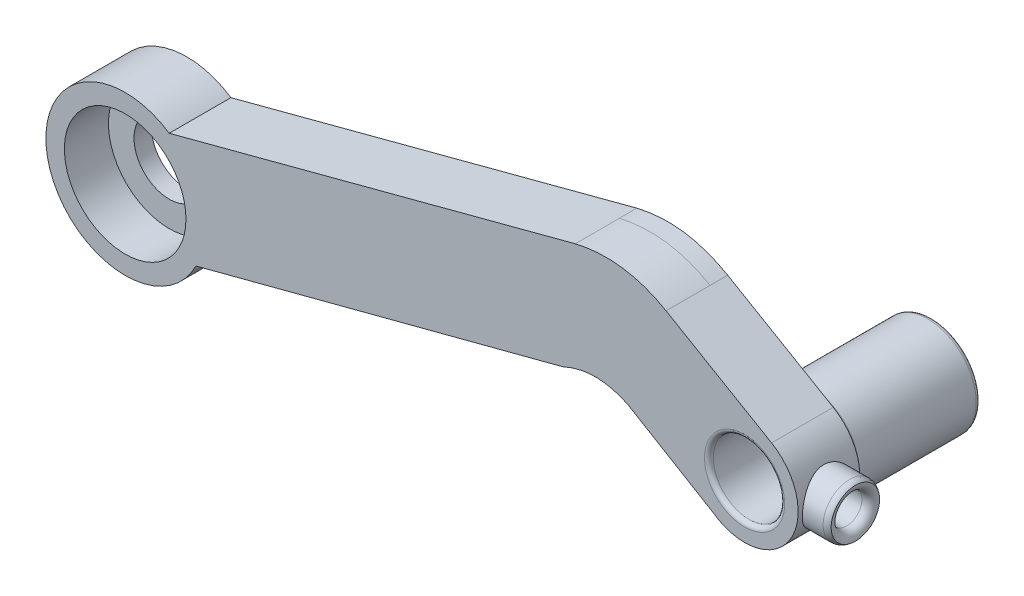
SolidWorks part; units mm, degrees
ref_plane "Front Plane" through (0, 0, 0) normal (0, 0, 1) x (1, 0, 0)
ref_plane "Top Plane" through (0, 0, 0) normal (0, 1, 0) x (1, 0, 0)
ref_plane "Right Plane" through (0, 0, 0) normal (1, 0, 0) x (0, 0, -1)
sketch "Sketch2" plane through (0, 0, 102.4316) normal (0, 0, 1) x (1, 0, 0)
  line L8 (-120.223, 48.1324) -> (-110.6681, 42.4279)
  line L9 (-169.3666, 37.3143) -> (-127.7161, 48.234)
  line L10 (-126.3187, 61.0272) -> (-172.4039, 48.8476)
  line L11 (-104.0278, 52.5928) -> (-116.0098, 59.5925)
  circle A2 centre (-107.0939, 47.3443) radius 4.05
  circle A3 centre (-177.4038, 41.3642) radius 6.9
  arc A5 (-110.6681, 42.4279) -> (-104.0278, 52.5928) centre (-107.0939, 47.3443) ccw
  arc A6 (-172.4039, 48.8476) -> (-169.3666, 37.3143) centre (-177.4038, 41.3642) ccw
  parabola Q4 (-127.7161, 48.234) -> (-120.223, 48.1324) focus (-123.8474, 45.2368) apex (-123.6641, 49.0843)
  parabola Q5 (-116.0098, 59.5925) -> (-126.3187, 61.0272) focus (-121.5094, 54.8565) apex (-120.2687, 61.2162)
extrude "Boss-Extrude1" add sketch "Sketch2" along normal blind 5
sketch "Sketch3" plane through (0, 0, 102.4316) normal (0, 0, -1) x (-1, 0, 0)
  line L4 (110.6681, 42.4279) -> (120.223, 48.1324)
  line L5 (127.7161, 48.234) -> (169.3666, 37.3143)
  line L6 (172.4039, 48.8476) -> (126.3187, 61.0272)
  line L7 (116.0098, 59.5925) -> (104.0278, 52.5928)
  line L8 (110.6681, 42.4279) -> (120.223, 48.1324)
  line L9 (127.7161, 48.234) -> (169.3666, 37.3143)
  line L10 (172.4039, 48.8476) -> (126.3187, 61.0272)
  line L11 (116.0098, 59.5925) -> (104.0278, 52.5928)
  circle A0 centre (107.0939, 47.3443) radius 4.05
  circle A1 centre (177.4038, 41.3642) radius 4
  arc A2 (104.0278, 52.5928) -> (110.6681, 42.4279) centre (107.0939, 47.3443) ccw
  arc A3 (169.3666, 37.3143) -> (172.4039, 48.8476) centre (177.4038, 41.3642) ccw
  arc A4 (104.0278, 52.5928) -> (110.6681, 42.4279) centre (107.0939, 47.3443) ccw
  arc A5 (169.3666, 37.3143) -> (172.4039, 48.8476) centre (177.4038, 41.3642) ccw
  parabola Q2 (120.223, 48.1324) -> (127.7161, 48.234) focus (123.8474, 45.2368) apex (123.6641, 49.0843)
  parabola Q3 (126.3187, 61.0272) -> (116.0098, 59.5925) focus (121.5094, 54.8565) apex (120.2687, 61.2162)
  parabola Q4 (120.223, 48.1324) -> (127.7161, 48.234) focus (123.8474, 45.2368) apex (123.6641, 49.0843)
  parabola Q5 (126.3187, 61.0272) -> (116.0098, 59.5925) focus (121.5094, 54.8565) apex (120.2687, 61.2162)
  dimension "D2" = 8.1
  dimension "D3" = 8
  dimension "D1" = 0
extrude "Boss-Extrude2" add sketch "Sketch3" along normal blind 2
sketch "Sketch5" plane through (0, 0, 100.4316) normal (0, 0, -1) x (-1, 0, 0)
  circle A0 centre (107.0939, 47.3443) radius 5.5
  circle A1 centre (107.0939, 47.3443) radius 4.05
  dimension "D1" = 11
  dimension "D2" = 8.1
extrude "Boss-Extrude3" add sketch "Sketch5" along normal blind 11.3
sketch "Sketch6" plane through (0, 0, 89.1316) normal (0, 0, -1) x (-1, 0, 0)
  circle A0 centre (107.0939, 47.3443) radius 5.5
  circle A1 centre (107.0939, 47.3443) radius 5.5 construction
  circle A2 centre (107.0939, 47.3443) radius 2.75
  dimension "D1" = 5.5
extrude "Boss-Extrude4" add sketch "Sketch6" along normal blind 3
fillet "Fillet1" radius 0.5 1 edges at (-112.5939, 47.3443, 100.4316)
fillet "Fillet2" radius 0.5 1 edges at (-112.5939, 47.3443, 86.1316)
fillet "Fillet3" radius 0.5 3 edges at (-103.0439, 47.3443, 107.4316) (-109.8439, 47.3443, 86.1316) (-109.8439, 47.3443, 89.1316)
ref_plane "Plane1" through (-101.0155, 0, 0) normal (1, 0, 0) x (0, 0, -1)
sketch "Sketch7" plane through (-101.0155, 0, 0) normal (1, 0, 0) x (0, 0, -1)
  circle A0 centre (-103.9316, 46.9294) radius 3
  dimension "D1" = 6
extrude "Boss-Extrude5" add sketch "Sketch7" along normal blind 3 and the other way blind 1
sketch "Sketch8" plane through (-98.0155, 0, 0) normal (1, 0, 0) x (0, 0, -1)
  circle A0 centre (-103.9316, 46.9294) radius 1.75
  dimension "D1" = 3.5
extrude "Cut-Extrude1" cut sketch "Sketch8" against normal blind 8
fillet "Fillet4" radius 1 1 edges at (-98.0155, 46.9294, 102.1816)
fillet "Fillet5" radius 1 1 edges at (-98.0155, 46.9294, 100.9316)
scale "Scale1" scale about centroid uniform scaling yes scale factor 1.5
